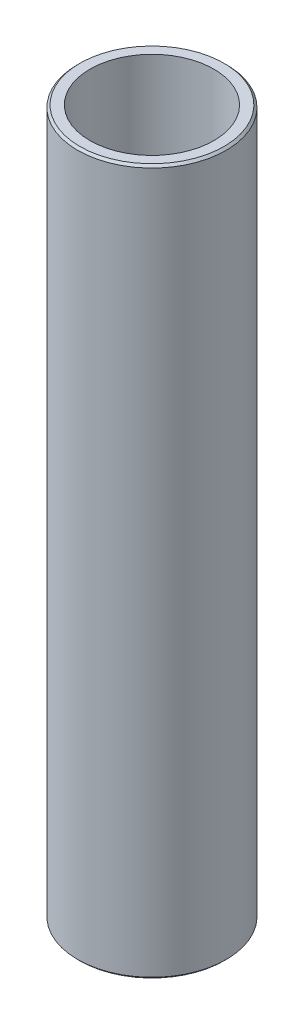
SolidWorks part; units mm, degrees
ref_plane "Front Plane" through (0, 0, 0) normal (0, 0, 1) x (1, 0, 0)
ref_plane "Top Plane" through (0, 0, 0) normal (0, 1, 0) x (1, 0, 0)
ref_plane "Right Plane" through (0, 0, 0) normal (1, 0, 0) x (0, 0, -1)
sketch "Sketch1" plane through (0, 0, 0) normal (0, 1, 0) x (1, 0, 0)
  circle A0 centre (0, 0) radius 42.5
  dimension "SHAFT_OD" = 85
extrude "Boss-Extrude1" add sketch "Sketch1" along normal blind 403.3056
sketch "Sketch2" plane through (0, 0, 0) normal (0, 1, 0) x (1, 0, 0)
  circle A0 centre (0, 0) radius 35.4422
  dimension "BORE_D" = 70.8844
extrude "Cut-Extrude1" cut sketch "Sketch2" along normal through all
chamfer "Chamfer1" distance 1.2667 angle 45 2 edges at (0, 403.3056, 42.5) (0, 0, 42.5)
